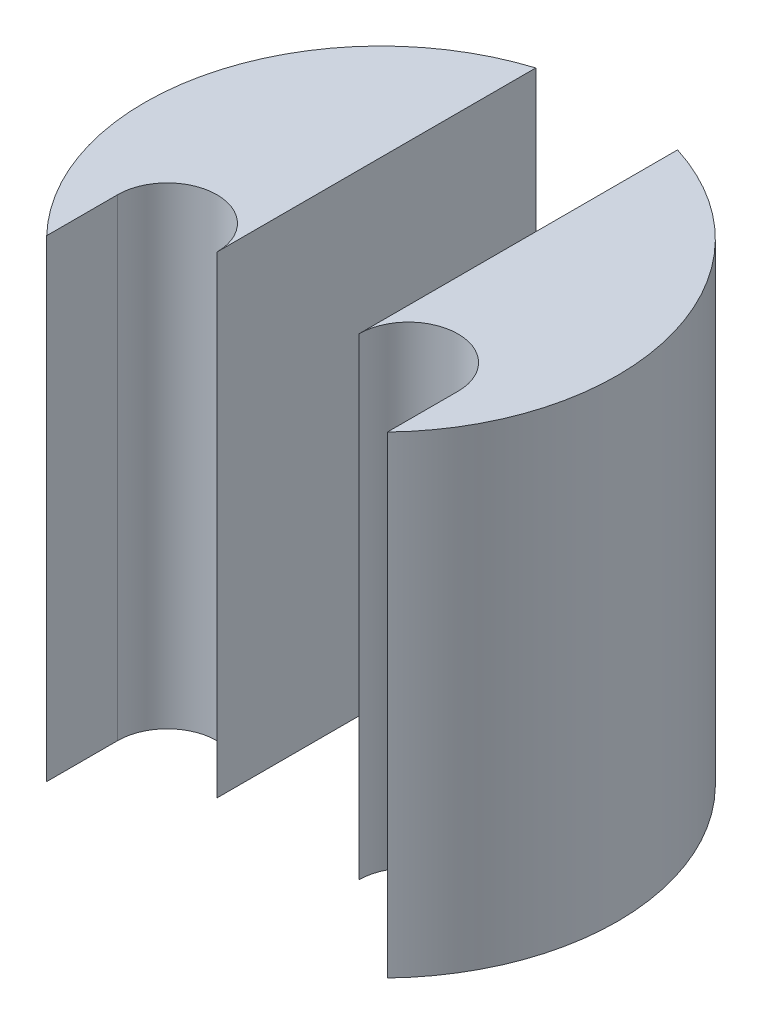
SolidWorks part; units mm, degrees
ref_plane "Front Plane" through (0, 0, 0) normal (0, 0, 1) x (1, 0, 0)
ref_plane "Top Plane" through (0, 0, 0) normal (0, 1, 0) x (1, 0, 0)
ref_plane "Right Plane" through (0, 0, 0) normal (1, 0, 0) x (0, 0, -1)
sketch "Sketch2" plane through (0, 0, 0) normal (0, 1, 0) x (1, 0, 0)
  line L0 (0.0632, -6.4631) -> (0.0632, -55.8981) construction
  line L1 (-29.9368, 95.4138) -> (-29.9368, -39.463)
  line L2 (30.0632, 95.374) -> (30.0632, -39.463)
  line L3 (-71.9368, -39.463) -> (-71.9368, -69.463)
  line L4 (72.0632, -39.463) -> (72.0632, -69.463)
  arc A0 (72.0632, -69.3317) -> (30.0632, 95.374) centre (0, 0) ccw
  arc A1 (-29.9368, -39.463) -> (-71.9368, -39.463) centre (-50.9368, -39.463) ccw
  arc A2 (30.0632, -39.463) -> (72.0632, -39.463) centre (51.0632, -39.463) cw
  arc A3 (-29.9368, 95.4138) -> (-71.9368, -69.463) centre (0, 0) ccw
  dimension "D1" = 100
  dimension "D5" = 42
  dimension "D2" = 30
  dimension "D3" = 164.8768
  dimension "D6" = 30
extrude "Boss-Extrude2" add sketch "Sketch2" along normal blind 200 contours L1 A3 L3 A1 | L2 A2 L4 A0 region at (-62.4571, 0, -19.5366) region at (62.5169, 0, -19.5555)
